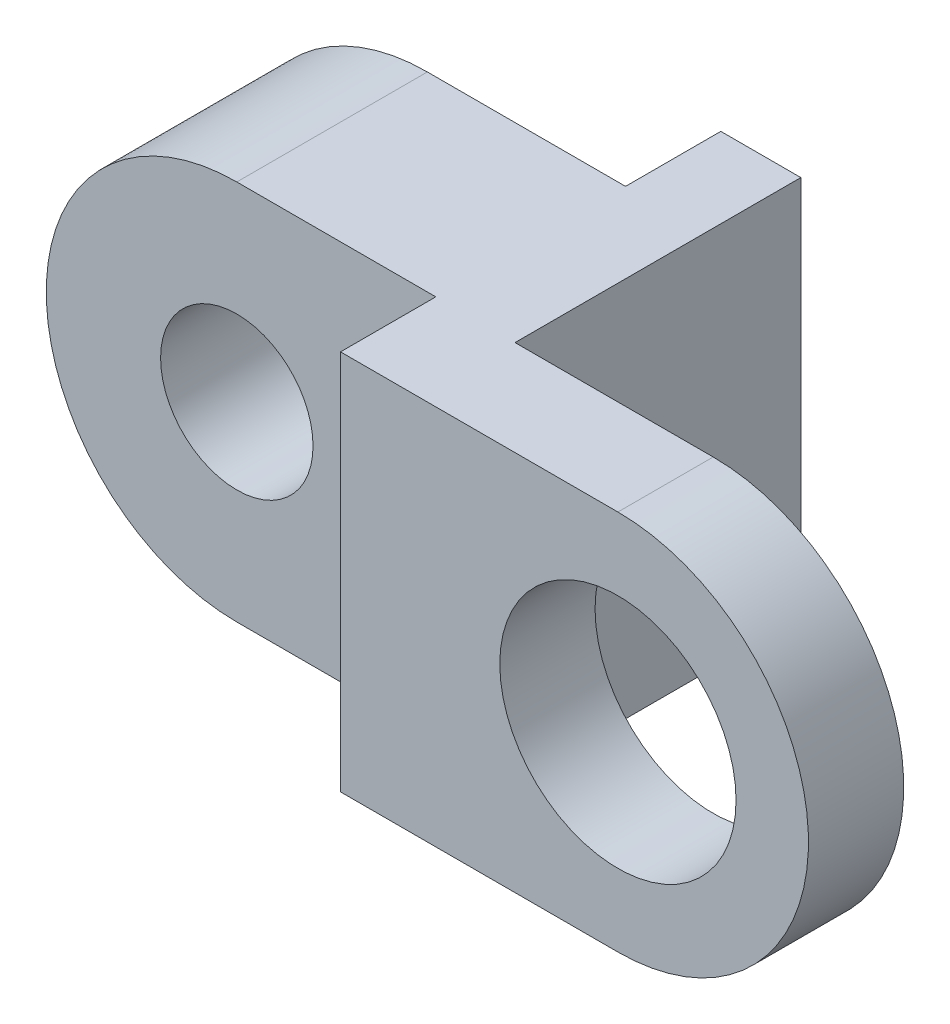
SolidWorks part; units mm, degrees
material "ABS"
ref_plane "前基準面" through (0, 0, 0) normal (0, 0, 1) x (1, 0, 0)
ref_plane "上基準面" through (0, 0, 0) normal (0, 1, 0) x (1, 0, 0)
ref_plane "右基準面" through (0, 0, 0) normal (1, 0, 0) x (0, 0, -1)
sketch "草圖1" plane through (0, 0, 0) normal (0, 0, 1) x (1, 0, 0)
  line L1 (-6.25, -5) -> (6.25, -5)
  line L3 (-6.25, 5) -> (6.25, 5)
  line L5 (-6.25, -5) -> (6.25, 5) construction
  line L6 (-6.25, 5) -> (6.25, -5) construction
  arc A0 (6.25, 5) -> (6.25, -5) centre (6.25, 0) cw
  arc A1 (-6.25, 5) -> (-6.25, -5) centre (-6.25, 0) ccw
  point P0 (0, 0)
  dimension "D1" = 10
  dimension "D2" = 12.5
extrude "填料-伸長1" add sketch "草圖1" along normal blind 10
sketch "草圖2" plane through (0, 0, 10) normal (0, 0, 1) x (1, 0, 0)
  circle A0 centre (-6.25, 0) radius 2
  circle A1 centre (6.25, 0) radius 3.1
  dimension "D1" = 4
  dimension "D2" = 6.2
sketch "草圖3" plane through (0, 5, 0) normal (0, 1, 0) x (1, 0, 0)
  line L0 (-1020, -5) -> (48980, -5) construction
  line L1 (-6.25, -10) -> (-6.25, 0) construction
  line L2 (11.25, -10) -> (11.25, 0) construction
  line L3 (6.25, -6.25) -> (11.25, -6.25)
  line L4 (6.25, -6.25) -> (6.25, -3.75)
  line L5 (6.25, -3.75) -> (11.25, -3.75)
  line L6 (11.25, -6.25) -> (11.25, -3.75)
  point P5 (-6.25, -5)
  dimension "D1" = 2.5
  dimension "D2" = 5
extrude "除料-伸長2" cut sketch "草圖3" against normal through all
sketch "草圖4" plane through (0, 5, 0) normal (0, 1, 0) x (1, 0, 0)
  line L0 (-6.25, -5) -> (-27.2142, -5) construction
  line L1 (-6.25, -10) -> (-6.25, 0) construction
  line L2 (-6.25, 0) -> (-11.25, 0) construction
  line L3 (-11.25, 0) -> (-1.05, 0)
  line L4 (-11.25, 0) -> (-11.25, -2.5)
  line L5 (-11.25, -2.5) -> (-1.05, -2.5)
  line L6 (-1.05, 0) -> (-1.05, -2.5)
  line L7 (-11.25, -7.5) -> (-1.0284, -7.5)
  line L8 (-1.0284, -10) -> (-1.0284, -7.5)
  line L9 (-11.25, -10) -> (-1.0284, -10)
  line L10 (-11.25, -10) -> (-11.25, -7.5)
  line L11 (6.25, -10) -> (-6.25, -10) construction
  line L16 (-11.25, 0) -> (-11.25, -10) construction
  line L18 (1.05, -7.5) -> (11.25, -7.5)
  line L19 (1.05, -7.5) -> (1.05, 0)
  line L20 (1.05, 0) -> (11.25, 0)
  line L21 (11.25, -7.5) -> (11.25, 0)
  dimension "D1" = 2.5
  dimension "D2" = 10.2
  dimension "D3" = 2.5
  dimension "D4" = 10.2
extrude "除料-伸長3" cut sketch "草圖4" against normal through all
extrude "填料-伸長2" add sketch "草圖2" against normal blind 3 from offset 1.5 contours A0 region at (-6.25, 0, 10) offset against normal yes
extrude "除料-伸長4" cut sketch "草圖2<3>" against normal through all contours A1 | A0 region at (6.25, 0, 10)
sketch "草圖2<3>" plane through (0, 0, 10) normal (0, 0, 1) x (1, 0, 0) same geometry as "草圖2"
chamfer "導角1" [suppressed] distance 0.3 angle 45
